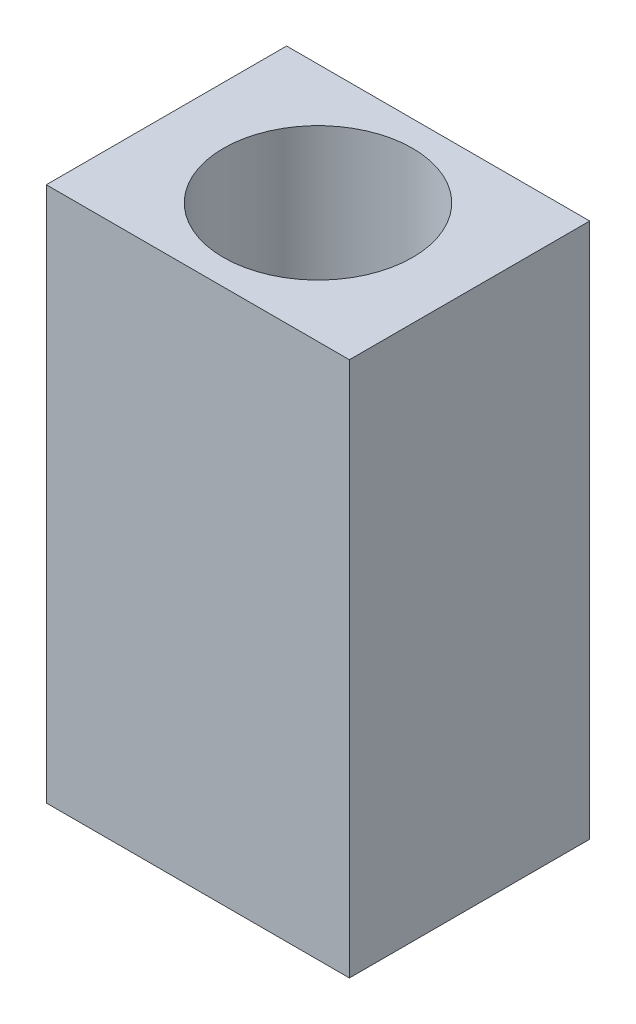
SolidWorks part; units mm, degrees
material "ABS"
ref_plane "Alzado" through (0, 0, 0) normal (0, 0, 1) x (1, 0, 0)
ref_plane "Planta" through (0, 0, 0) normal (0, 1, 0) x (1, 0, 0)
ref_plane "Vista lateral" through (0, 0, 0) normal (1, 0, 0) x (0, 0, -1)
sketch "Sketch1" plane through (0, 0, 0) normal (0, 1, 0) x (1, 0, 0)
  line L1 (-4.2457, -3.3661) -> (4.2457, -3.3661)
  line L2 (-4.2457, -3.3661) -> (-4.2457, 3.3661)
  line L3 (-4.2457, 3.3661) -> (4.2457, 3.3661)
  line L4 (4.2457, -3.3661) -> (4.2457, 3.3661)
  line L5 (-4.2457, -3.3661) -> (4.2457, 3.3661) construction
  line L6 (-4.2457, 3.3661) -> (4.2457, -3.3661) construction
  circle A0 centre (0, 0) radius 2.5
  dimension "D1" = 5
extrude "Boss-Extrude1" add sketch "Sketch1" along normal blind 15
sketch "Sketch2" plane through (0, 15, 0) normal (0, 1, 0) x (1, 0, 0)
  point P0 (0, 0)
hole_wizard "Taladro de margen para M51" positions "Sketch2" profile "Sketch3" hole size "M5" standard "ISO" end condition through all
sketch "Sketch3" plane through (0, 15, 0) normal (1, 0, 0) x (0, 0, 1)
  line L0 (0, 0) -> (0, 15)
  line L1 (0, 15) -> (2.65, 15)
  line L2 (2.65, 15) -> (2.65, 0)
  line L5 (2.65, 0) -> (0, 0)
  line L11 (0, -6.35) -> (0, 107.95) construction
  dimension "Diámetro de taladro hasta el siguiente" = 5.3
  dimension "Profundidad de taladro hasta el siguiente" = 15
